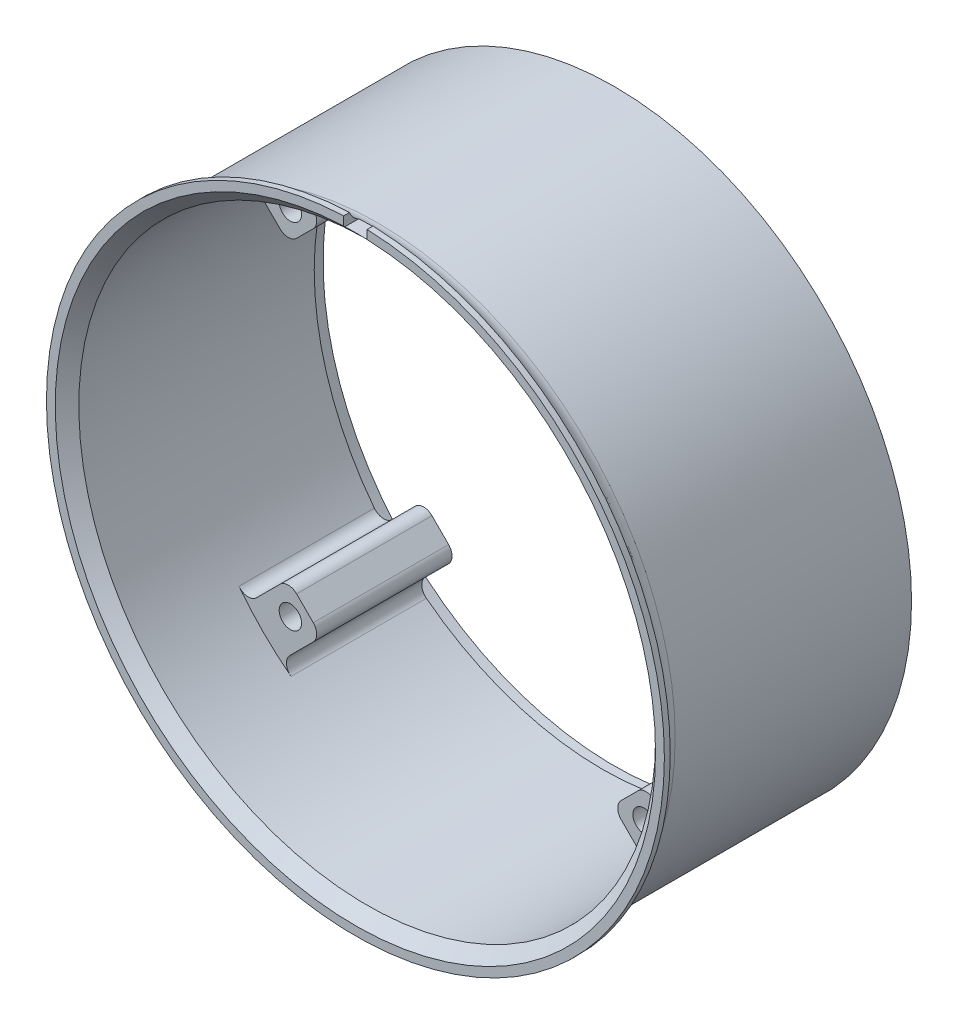
SolidWorks part; units mm, degrees
ref_plane "Front Plane" through (0, 0, 0) normal (0, 0, 1) x (1, 0, 0)
ref_plane "Top Plane" through (0, 0, 0) normal (0, 1, 0) x (1, 0, 0)
ref_plane "Right Plane" through (0, 0, 0) normal (1, 0, 0) x (0, 0, -1)
sketch "Sketch1" plane through (0, 0, 0) normal (0, 0, 1) x (1, 0, 0)
  circle A0 centre (0, 0) radius 50.5
  circle A1 centre (0, 0) radius 52.5
  circle A2 centre (0, 0) radius 49
  dimension "D1" = 101
  dimension "D2" = 105
  dimension "D3" = 98
sketch "Sketch2" plane through (0, 0, 0) normal (0, 0, 1) x (1, 0, 0)
  circle A0 centre (0, 0) radius 50.5
  circle A1 centre (0, 0) radius 50.5 construction
extrude "Boss-Extrude2" add sketch "Sketch2" along normal blind 2
sketch "Sketch3" plane through (0, 0, 2) normal (0, 0, 1) x (1, 0, 0)
  circle A0 centre (0, 0) radius 50.5
  circle A1 centre (0, 0) radius 49
  circle A2 centre (0, 0) radius 50.5 construction
  circle A3 centre (0, 0) radius 49 construction
extrude "Boss-Extrude3" add sketch "Sketch3" along normal blind 42
sketch "Sketch4" plane through (0, 0, 44) normal (0, 0, 1) x (1, 0, 0)
  circle A0 centre (0, 0) radius 49
  circle A1 centre (0, 0) radius 52.5
  circle A2 centre (0, 0) radius 52.5 construction
  circle A3 centre (0, 0) radius 49 construction
extrude "Boss-Extrude4" add sketch "Sketch4" against normal blind 1
fillet "Fillet1" radius 3 1 edges at (50.5, 0, 43)
chamfer "Chamfer1" distance 2 angle 45 1 edges at (49, 0, 44)
sketch "Sketch5" plane through (0, 0, 0) normal (0, 0, 1) x (1, 0, 0)
  line L0 (0, 25.6235) -> (0, 7.7889) construction
  line L1 (-88.8622, 20) -> (-31.0742, 20) construction
  line L2 (3, 20) -> (3, 19.4348) construction
  line L3 (7, 20) -> (7, 19.6279) construction
  line L4 (-3, 20) -> (-3, 23.2508) construction
  line L5 (-6.5, 20) -> (-6.5, 23.6279) construction
  line L6 (0, 28) -> (-19.0387, 28) construction
  line L7 (0, 12) -> (-19.0387, 12) construction
  line L8 (0, 23) -> (-18.6123, 23) construction
  line L9 (0, 17) -> (-19.0387, 17) construction
  line L10 (13.075, 20) -> (13.075, 22.7042) construction
  line L11 (-13.325, 20) -> (-13.325, 25.8844) construction
  circle A0 centre (0, 20) radius 3
  circle A1 centre (0, 10) radius 2
  circle A2 centre (0, 30) radius 2
  circle A3 centre (10.125, 20) radius 3.125
  circle A4 centre (-10.125, 20) radius 3.625
  circle A5 centre (-10.125, 20) radius 3.2 construction
  circle A6 centre (10.125, 20) radius 2.95 construction
  dimension "D1" = 6
  dimension "D2" = 4
  dimension "D3" = 4
  dimension "D4" = 6.25
  dimension "D5" = 7.25
  dimension "D11" = 6.4
  dimension "D12" = 5.9
  dimension "D6" = 4
  dimension "D7" = 3.5
  dimension "D8" = 5
  dimension "D9" = 5
  dimension "D10" = 10
  dimension "D13" = 26.4
extrude "Cut-Extrude3" cut sketch "Sketch5" along normal through all contours A4 | A0 | A3 | A2 | A1
pattern_circular "CirPattern1" count 4 over 360 about axis through (0, 0, 2) along (0, 0, -1) of "Cut-Extrude3"
sketch "Sketch6" plane through (0, 0, 0) normal (0, 0, -1) x (-1, 0, 0)
  line L0 (20, 0) -> (20, 16.1509) construction
  line L1 (0, 20) -> (-19.1479, 20) construction
  line L2 (-20, 0) -> (-20, 17.3971) construction
  line L3 (0, -20) -> (22.3917, -20) construction
  line L4 (0, 20) -> (-20.9516, 40.9516)
  line L5 (0, 20) -> (20.9516, 40.9516)
  line L6 (0, 0) -> (0, 59.0315) construction
  line L7 (0, 0) -> (60.9979, 0) construction
  line L8 (20, 0) -> (40.9516, 20.9516)
  line L9 (20, 0) -> (40.9516, -20.9516)
  line L10 (-20, 0) -> (-40.9516, 20.9516)
  line L11 (-20, 0) -> (-40.9516, -20.9516)
  line L12 (0, -20) -> (-20.9516, -40.9516)
  line L13 (0, -20) -> (20.9516, -40.9516)
  line L14 (-35.8697, 28.7987) -> (-30.4056, 23.3345)
  line L15 (-30.4056, 23.3345) -> (-23.3345, 30.4056)
  line L16 (-23.3345, 30.4056) -> (-28.7987, 35.8697)
  line L17 (0, 0) -> (-47.992, 47.992) construction
  line L18 (0, 0) -> (52.7868, 52.7868) construction
  line L19 (28.7987, 35.8697) -> (23.3345, 30.4056)
  line L20 (23.3345, 30.4056) -> (30.4056, 23.3345)
  line L21 (30.4056, 23.3345) -> (35.8697, 28.7987)
  line L22 (28.7987, -35.8697) -> (23.3345, -30.4056)
  line L23 (23.3345, -30.4056) -> (30.4056, -23.3345)
  line L24 (30.4056, -23.3345) -> (35.8697, -28.7987)
  line L25 (-35.8697, -28.7987) -> (-30.4056, -23.3345)
  line L26 (-30.4056, -23.3345) -> (-23.3345, -30.4056)
  line L27 (-23.3345, -30.4056) -> (-28.7987, -35.8697)
  circle A0 centre (0, 20) radius 14
  circle A1 centre (20, 0) radius 14
  circle A2 centre (0, -20) radius 14
  circle A3 centre (-20, 0) radius 14
  circle A4 centre (-15, 20) radius 1
  circle A5 centre (15, 20) radius 1.0367
  circle A6 centre (20, 15) radius 1
  circle A7 centre (20, -15) radius 1
  circle A8 centre (15, -20) radius 1
  circle A9 centre (-15, -20) radius 1
  circle A10 centre (-20, 15) radius 1
  circle A11 centre (-20, -15) radius 1
  circle A12 centre (0, 0) radius 46
  circle A13 centre (0, 20) radius 2.5
  circle A14 centre (-20, 0) radius 2.5
  circle A15 centre (20, 0) radius 2.5
  circle A16 centre (0, -20) radius 2.5
  point P39 (0, 46)
  point P63 (-26.8701, 26.8701)
  point P65 (-32.5269, 32.5269)
  point P67 (26.8701, 26.8701)
  point P71 (32.5269, 32.5269)
  point P79 (26.8701, -26.8701)
  point P81 (32.5269, -32.5269)
  point P82 (-32.5269, -32.5269)
  point P85 (-26.8701, -26.8701)
  dimension "D1" = 28
  dimension "D2" = 28
  dimension "D3" = 28
  dimension "D4" = 28
  dimension "D5" = 2
  dimension "D6" = 2
  dimension "D7" = 2.0734
  dimension "D8" = 2
  dimension "D9" = 2
  dimension "D10" = 2
  dimension "D11" = 2
  dimension "D12" = 2
  dimension "D17" = 15
  dimension "D26" = 5
  dimension "D27" = 5
  dimension "D28" = 5
  dimension "D29" = 5
  dimension "D13" = 15
  dimension "D14" = 15
  dimension "D15" = 15
  dimension "D16" = 15
  dimension "D18" = 15
  dimension "D19" = 15
  dimension "D20" = 15
  dimension "D21" = 26
  dimension "D22" = 45
  dimension "D23" = 45
  dimension "D24" = 45
  dimension "D25" = 45
  dimension "D30" = 45
  dimension "D31" = 45
  dimension "D32" = 10
  dimension "D33" = 8
  dimension "D34" = 10
  dimension "D35" = 8
  dimension "D36" = 10
  dimension "D37" = 8
  dimension "D38" = 8
  dimension "D39" = 10
sketch "Sketch7" plane through (0, 0, 0) normal (0, 0, -1) x (-1, 0, 0)
  line L0 (31.7042, 37.361) -> (24.7487, 30.4056)
  line L1 (24.7487, 30.4056) -> (30.4056, 24.7487)
  line L2 (30.4056, 24.7487) -> (37.361, 31.7042)
  line L3 (20.7719, 20.7719) -> (14.7081, 14.7081) construction
  line L4 (0, 0) -> (62.5427, 0) construction
  line L5 (30.437, 38.8595) -> (21.345, 47.9515) construction
  circle A0 centre (0, 0) radius 49 construction
  arc A1 (37.361, 31.7042) -> (31.7042, 37.361) centre (0, 0) ccw
  point P14 (34.6482, 34.6482)
  dimension "D1" = 45
  dimension "D2" = 8
  dimension "D3" = 4
  dimension "D4" = 10
ref_plane "Plane1" through (0, 0, 42) normal (0, 0, 1) x (1, 0, 0)
ref_plane "Plane2" through (0, 0, 38) normal (0, 0, 1) x (1, 0, 0)
sketch "Sketch8" plane through (0, 0, 38) normal (0, 0, 1) x (1, 0, 0)
  circle A0 centre (0, 0) radius 50
  circle A1 centre (0, 0) radius 46
  dimension "D1" = 100
  dimension "D2" = 4
extrude "Boss-Extrude6" add sketch "Sketch7" against normal blind 25 contours L2 A1 L0 L1
fillet "Fillet3" radius 2 4 edges at (-30.4056, 24.7487, 13.5) (-37.361, 31.7042, 13.5) (-24.7487, 30.4056, 13.5) (-31.7042, 37.361, 13.5)
pattern_circular "CirPattern2" count 4 over 360 about axis through (0, 0, 2) along (0, 0, -1) of "Fillet3", "Boss-Extrude6"
sketch "Sketch9" plane through (0, 0, 0) normal (0, 0, 1) x (1, 0, 0)
  line L0 (-2, 52.4619) -> (-2, 50.75)
  line L1 (-2, 50.75) -> (2, 50.75)
  line L2 (2, 50.75) -> (2, 52.4619)
  line L3 (-3.1797, 52.5) -> (3.1797, 52.5) construction
  circle A0 centre (0, 0) radius 52.5 construction
  arc A1 (2, 52.4619) -> (-2, 52.4619) centre (0, 0) ccw
  point P4 (0, 50.75)
  point P10 (0, 52.5)
  point P12 (0, 52.5)
  dimension "D1" = 4
  dimension "D2" = 1.75
extrude "Cut-Extrude4" cut sketch "Sketch9" along normal through all
sketch "Sketch10" plane through (0, 0, 0) normal (0, 0, 1) x (1, 0, 0)
  line L0 (-27.5772, 27.5772) -> (-29.2234, 29.2234) construction
  line L2 (-28.9914, 26.163) -> (-26.163, 28.9914) construction
  line L3 (-30.1337, 35.7905) -> (-26.163, 31.8198) construction
  circle A0 centre (-30.052, 30.052) radius 1.9
  point P0 (-30.052, 30.052)
  point P5 (-27.5772, 27.5772)
  dimension "D1" = 3.8
  dimension "D2" = 3.5
sketch "Sketch11" plane through (0, 0, 0) normal (0, 0, 1) x (1, 0, 0)
  line L2 (-18.825, 0) -> (18.825, 0) construction
  circle A0 centre (19.95, 0) radius 1.125
  circle A1 centre (-19.95, 0) radius 1.125
  point P5 (0, 0)
  dimension "D1" = 2.25
  dimension "D2" = 2.25
  dimension "D3" = 37.65
sketch "Sketch12" plane through (0, 0, 0) normal (0, 0, 1) x (1, 0, 0)
  circle A0 centre (0, 0) radius 49.5
  dimension "D1" = 99
extrude "Cut-Extrude5" cut sketch "Sketch12" along normal blind 2
extrude "Cut-Extrude6" cut sketch "Sketch10" along normal up to next contours A0
pattern_circular "CirPattern3" count 4 over 360 about axis through (0, 0, 2) along (0, 0, -1) of "Cut-Extrude6"
